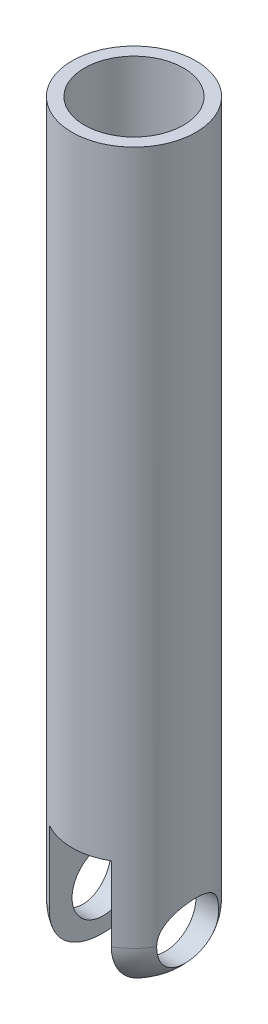
SolidWorks part; units mm, degrees
material "AISI 1020"
ref_plane "Front" through (0, 0, 0) normal (0, 0, 1) x (1, 0, 0)
ref_plane "Top" through (0, 0, 0) normal (0, 1, 0) x (1, 0, 0)
ref_plane "Right" through (0, 0, 0) normal (1, 0, 0) x (0, 0, -1)
sketch "Sketch1" plane through (0, 0, 0) normal (0, 1, 0) x (1, 0, 0)
  circle A0 centre (0, 0) radius 5
  circle A1 centre (0, 0) radius 4
  dimension "D1" = 10
  dimension "D2" = 8
extrude "Boss-Extrude1" add sketch "Sketch1" along normal blind 50 contours A0
extrude "Cut-Extrude1" cut sketch "Sketch1<3>" along normal blind 50 from offset 4 contours A1
sketch "Sketch1<3>" plane through (0, 0, 0) normal (0, 1, 0) x (1, 0, 0) same geometry as "Sketch1"
sketch "Sketch2" plane through (0, 0, 0) normal (0, -1, 0) x (1, 0, 0)
  line L1 (0, -5) -> (0, -7.3769) construction
  line L3 (-2.5, 4.3301) -> (-2.5, -4.3301)
  line L5 (2.5, 4.3301) -> (2.5, -4.3301)
  arc A0 (2.5, -4.3301) -> (2.5, 4.3301) centre (0, 0) ccw
  arc A1 (-2.5, 4.3301) -> (-2.5, -4.3301) centre (0, 0) ccw
extrude "Boss-Extrude2" add sketch "Sketch2" along normal blind 10 contours L3 A1 | L5 A0
fillet "Fillet3" radius 4 2 edges at (-5, -10, 0) (5, -10, 0)
sketch "Sketch3" plane through (-2.5, 0, 0) normal (1, 0, 0) x (0, 0, -1)
  line L0 (-4.3301, -6) -> (4.3301, -6) construction
  circle A0 centre (0, -6) radius 2.5
  dimension "D1" = 5
extrude "Cut-Extrude2" cut sketch "Sketch3" against normal through all both and the other way through all contours A0
